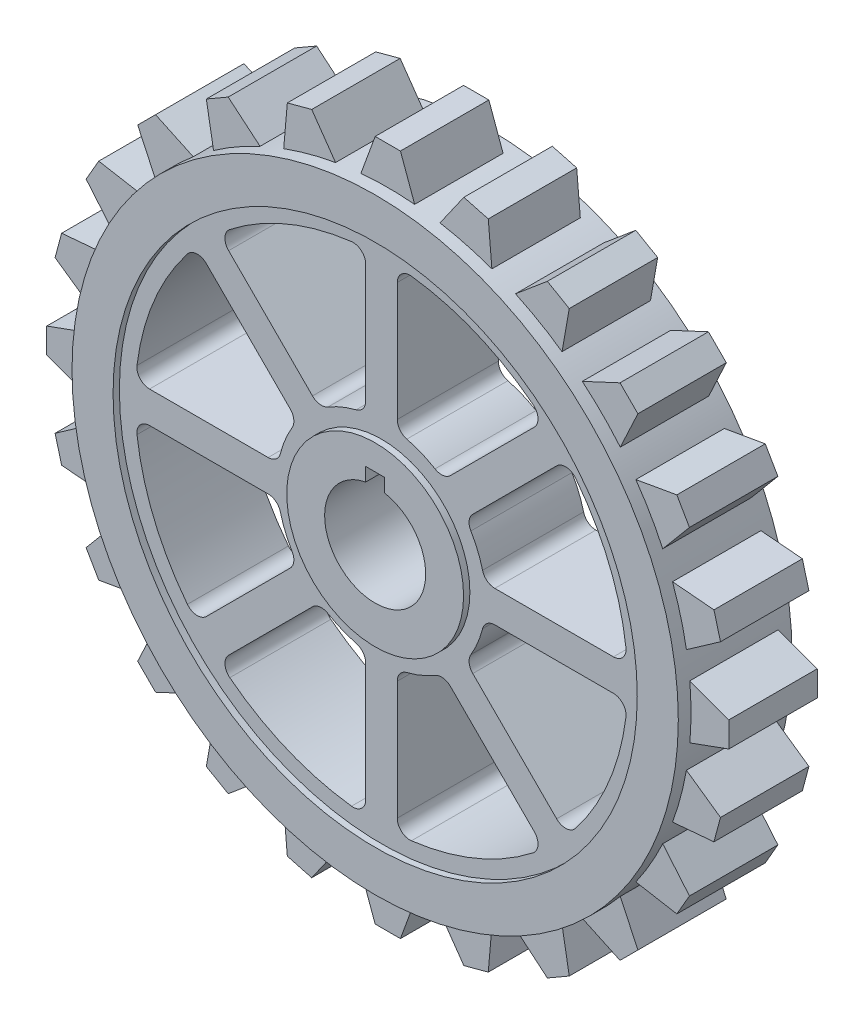
SolidWorks part; units mm, degrees
ref_plane "Front Plane" through (0, 0, 0) normal (0, 0, 1) x (1, 0, 0)
ref_plane "Top Plane" through (0, 0, 0) normal (0, 1, 0) x (1, 0, 0)
ref_plane "Right Plane" through (0, 0, 0) normal (1, 0, 0) x (0, 0, -1)
sketch "Sketch1" plane through (0, 0, 0) normal (0, 0, 1) x (1, 0, 0)
  line L0 (-1024.8275, 0) -> (-48, 0) construction
  line L1 (-1.5, 10) -> (1.5, 10)
  line L2 (-1.5, 10) -> (-1.5, 7.8581)
  line L3 (1.5, 10) -> (1.5, 7.8581)
  line L4 (0, 0) -> (0, 14)
  line L5 (-2.5, 36.7253) -> (-2.5, 17.9444)
  line L6 (0, 0) -> (0, 14)
  line L7 (24.201, 27.7365) -> (10.9208, 14.4563)
  line L8 (0, 0) -> (-25.7527, 25.7527) construction
  line L9 (-24.201, 27.7365) -> (-10.9208, 14.4563)
  line L10 (36.7253, 2.5) -> (17.9444, 2.5)
  line L11 (27.7365, 24.201) -> (14.4563, 10.9208)
  line L13 (2.5, 36.7253) -> (2.5, 17.9444)
  line L14 (-36.7253, 2.5) -> (-17.9444, 2.5)
  line L15 (0, 54) -> (0, 48) construction
  line L16 (-2, 54) -> (2, 54)
  line L17 (-2, 54) -> (-4.2525, 47.8113)
  line L18 (2, 54) -> (4.2525, 47.8113)
  line L19 (12.0444, 52.6776) -> (8.2668, 47.2828)
  line L20 (12.0444, 52.6776) -> (15.9081, 51.6424)
  line L21 (15.9081, 51.6424) -> (16.4821, 45.0815)
  line L22 (25.2679, 47.7654) -> (20.2228, 43.532)
  line L23 (25.2679, 47.7654) -> (28.7321, 45.7654)
  line L24 (28.7321, 45.7654) -> (27.5884, 39.2795)
  line L25 (36.7696, 39.598) -> (30.8007, 36.8146)
  line L26 (36.7696, 39.598) -> (39.598, 36.7696)
  line L27 (39.598, 36.7696) -> (36.8146, 30.8007)
  line L28 (45.7654, 28.7321) -> (39.2795, 27.5884)
  line L29 (45.7654, 28.7321) -> (47.7654, 25.2679)
  line L30 (47.7654, 25.2679) -> (43.532, 20.2228)
  line L31 (51.6424, 15.9081) -> (45.0815, 16.4821)
  line L32 (51.6424, 15.9081) -> (52.6776, 12.0444)
  line L33 (52.6776, 12.0444) -> (47.2828, 8.2668)
  line L34 (54, 2) -> (47.8113, 4.2525)
  line L35 (54, 2) -> (54, -2)
  line L36 (54, -2) -> (47.8113, -4.2525)
  line L37 (52.6776, -12.0444) -> (47.2828, -8.2668)
  line L38 (52.6776, -12.0444) -> (51.6424, -15.9081)
  line L39 (51.6424, -15.9081) -> (45.0815, -16.4821)
  line L40 (47.7654, -25.2679) -> (43.532, -20.2228)
  line L41 (47.7654, -25.2679) -> (45.7654, -28.7321)
  line L42 (45.7654, -28.7321) -> (39.2795, -27.5884)
  line L43 (39.598, -36.7696) -> (36.8146, -30.8007)
  line L44 (39.598, -36.7696) -> (36.7696, -39.598)
  line L45 (36.7696, -39.598) -> (30.8007, -36.8146)
  line L46 (28.7321, -45.7654) -> (27.5884, -39.2795)
  line L47 (28.7321, -45.7654) -> (25.2679, -47.7654)
  line L48 (25.2679, -47.7654) -> (20.2228, -43.532)
  line L49 (15.9081, -51.6424) -> (16.4821, -45.0815)
  line L50 (15.9081, -51.6424) -> (12.0444, -52.6776)
  line L51 (12.0444, -52.6776) -> (8.2668, -47.2828)
  line L52 (2, -54) -> (4.2525, -47.8113)
  line L53 (2, -54) -> (-2, -54)
  line L54 (-2, -54) -> (-4.2525, -47.8113)
  line L55 (-12.0444, -52.6776) -> (-8.2668, -47.2828)
  line L56 (-12.0444, -52.6776) -> (-15.9081, -51.6424)
  line L57 (-15.9081, -51.6424) -> (-16.4821, -45.0815)
  line L58 (-25.2679, -47.7654) -> (-20.2228, -43.532)
  line L59 (-25.2679, -47.7654) -> (-28.7321, -45.7654)
  line L60 (-28.7321, -45.7654) -> (-27.5884, -39.2795)
  line L61 (-36.7696, -39.598) -> (-30.8007, -36.8146)
  line L62 (-36.7696, -39.598) -> (-39.598, -36.7696)
  line L63 (-39.598, -36.7696) -> (-36.8146, -30.8007)
  line L64 (-45.7654, -28.7321) -> (-39.2795, -27.5884)
  line L65 (-45.7654, -28.7321) -> (-47.7654, -25.2679)
  line L66 (-47.7654, -25.2679) -> (-43.532, -20.2228)
  line L67 (-51.6424, -15.9081) -> (-45.0815, -16.4821)
  line L68 (-51.6424, -15.9081) -> (-52.6776, -12.0444)
  line L69 (-52.6776, -12.0444) -> (-47.2828, -8.2668)
  line L70 (-54, -2) -> (-47.8113, -4.2525)
  line L71 (-54, -2) -> (-54, 2)
  line L72 (-54, 2) -> (-47.8113, 4.2525)
  line L73 (-52.6776, 12.0444) -> (-47.2828, 8.2668)
  line L74 (-52.6776, 12.0444) -> (-51.6424, 15.9081)
  line L75 (-51.6424, 15.9081) -> (-45.0815, 16.4821)
  line L76 (-47.7654, 25.2679) -> (-43.532, 20.2228)
  line L77 (-47.7654, 25.2679) -> (-45.7654, 28.7321)
  line L78 (-45.7654, 28.7321) -> (-39.2795, 27.5884)
  line L79 (-39.598, 36.7696) -> (-36.8146, 30.8007)
  line L80 (-39.598, 36.7696) -> (-36.7696, 39.598)
  line L81 (-36.7696, 39.598) -> (-30.8007, 36.8146)
  line L82 (-28.7321, 45.7654) -> (-27.5884, 39.2795)
  line L83 (-28.7321, 45.7654) -> (-25.2679, 47.7654)
  line L84 (-25.2679, 47.7654) -> (-20.2228, 43.532)
  line L85 (-15.9081, 51.6424) -> (-16.4821, 45.0815)
  line L86 (-15.9081, 51.6424) -> (-12.0444, 52.6776)
  line L87 (-12.0444, 52.6776) -> (-8.2668, 47.2828)
  line L88 (-27.7365, 24.201) -> (-14.4563, 10.9208)
  line L89 (-24.201, 27.7365) -> (-10.9208, 14.4563)
  line L90 (36.7253, -2.5) -> (17.9444, -2.5)
  line L91 (27.7365, -24.201) -> (14.4563, -10.9208)
  line L92 (24.201, -27.7365) -> (10.9208, -14.4563)
  line L93 (2.5, -36.7253) -> (2.5, -17.9444)
  line L94 (-2.5, -36.7253) -> (-2.5, -17.9444)
  line L95 (-24.201, -27.7365) -> (-10.9208, -14.4563)
  line L96 (-27.7365, -24.201) -> (-14.4563, -10.9208)
  line L97 (-36.7253, -2.5) -> (-17.9444, -2.5)
  line L98 (-14, 0) -> (24.8275, 0) construction
  arc A0 (-1.5, 7.8581) -> (1.5, 7.8581) centre (0, 0) ccw
  circle A1 centre (0, 0) radius 14
  circle A2 centre (0, 0) radius 41.5
  circle A3 centre (0, 0) radius 48
  circle A4 centre (0, 0) radius 48
  circle A5 centre (0, 0) radius 48
  circle A6 centre (0, 0) radius 48
  circle A7 centre (0, 0) radius 48
  circle A8 centre (0, 0) radius 48
  circle A9 centre (0, 0) radius 48
  circle A10 centre (0, 0) radius 48
  circle A11 centre (0, 0) radius 48
  circle A12 centre (0, 0) radius 48
  circle A13 centre (0, 0) radius 48
  circle A14 centre (0, 0) radius 48
  circle A15 centre (0, 0) radius 48
  circle A16 centre (0, 0) radius 48
  circle A17 centre (0, 0) radius 48
  circle A18 centre (0, 0) radius 48
  circle A19 centre (0, 0) radius 48
  circle A20 centre (0, 0) radius 48
  circle A21 centre (0, 0) radius 48
  circle A22 centre (0, 0) radius 48
  circle A23 centre (0, 0) radius 48
  circle A24 centre (0, 0) radius 48
  circle A25 centre (0, 0) radius 48
  circle A26 centre (0, 0) radius 48
  arc A27 (30.7264, -24.0185) -> (38.7105, -4.7432) centre (0, 0) ccw
  arc A28 (-36.7253, 2.5) -> (-38.7105, 4.7432) centre (-36.7253, 4.5) cw
  circle A29 centre (0, 0) radius 39 construction
  arc A30 (-27.7365, 24.201) -> (-30.7264, 24.0185) centre (-29.1507, 22.7868) ccw
  arc A31 (-30.7264, 24.0185) -> (-38.7105, 4.7432) centre (0, 0) ccw
  arc A32 (-24.0185, 30.7264) -> (-4.7432, 38.7105) centre (0, 0) cw
  arc A33 (-24.201, 27.7365) -> (-24.0185, 30.7264) centre (-22.7868, 29.1507) cw
  arc A34 (-2.5, 36.7253) -> (-4.7432, 38.7105) centre (-4.5, 36.7253) ccw
  arc A35 (-14.4563, 10.9208) -> (-14.1548, 8.4789) centre (-15.8706, 9.5066) cw
  arc A36 (-14.1548, 8.4789) -> (-16.0044, 4.0135) centre (0, 0) ccw
  arc A37 (-4.0135, 16.0044) -> (-8.4789, 14.1548) centre (0, 0) ccw
  arc A38 (17.9444, 2.5) -> (16.0044, 4.0135) centre (17.9444, 4.5) cw
  arc A39 (8.4789, 14.1548) -> (4.0135, 16.0044) centre (0, 0) ccw
  arc A40 (16.0044, 4.0135) -> (14.1548, 8.4789) centre (0, 0) ccw
  arc A41 (10.9208, -14.4563) -> (8.4789, -14.1548) centre (9.5066, -15.8706) ccw
  arc A42 (2.5, -17.9444) -> (4.0135, -16.0044) centre (4.5, -17.9444) cw
  arc A43 (36.7253, 2.5) -> (38.7105, 4.7432) centre (36.7253, 4.5) ccw
  arc A44 (30.7264, 24.0185) -> (38.7105, 4.7432) centre (0, 0) cw
  arc A45 (27.7365, 24.201) -> (30.7264, 24.0185) centre (29.1507, 22.7868) cw
  arc A46 (24.201, 27.7365) -> (24.0185, 30.7264) centre (22.7868, 29.1507) ccw
  arc A47 (2.5, 36.7253) -> (4.7432, 38.7105) centre (4.5, 36.7253) cw
  arc A48 (-4.7432, 38.7105) -> (-24.0185, 30.7264) centre (0, 0) ccw
  arc A49 (24.0185, 30.7264) -> (4.7432, 38.7105) centre (0, 0) ccw
  arc A50 (17.9444, -2.5) -> (16.0044, -4.0135) centre (17.9444, -4.5) ccw
  arc A51 (36.7253, -2.5) -> (38.7105, -4.7432) centre (36.7253, -4.5) cw
  arc A52 (27.7365, -24.201) -> (30.7264, -24.0185) centre (29.1507, -22.7868) ccw
  arc A53 (14.4563, -10.9208) -> (14.1548, -8.4789) centre (15.8706, -9.5066) cw
  arc A54 (24.201, -27.7365) -> (24.0185, -30.7264) centre (22.7868, -29.1507) cw
  arc A55 (24.0185, -30.7264) -> (4.7432, -38.7105) centre (0, 0) cw
  arc A56 (2.5, -36.7253) -> (4.7432, -38.7105) centre (4.5, -36.7253) ccw
  arc A57 (14.1548, -8.4789) -> (16.0044, -4.0135) centre (0, 0) ccw
  arc A58 (4.0135, -16.0044) -> (8.4789, -14.1548) centre (0, 0) ccw
  arc A59 (-8.4789, -14.1548) -> (-4.0135, -16.0044) centre (0, 0) ccw
  arc A60 (-2.5, -36.7253) -> (-4.7432, -38.7105) centre (-4.5, -36.7253) cw
  arc A61 (-24.0185, -30.7264) -> (-4.7432, -38.7105) centre (0, 0) ccw
  arc A62 (-24.201, -27.7365) -> (-24.0185, -30.7264) centre (-22.7868, -29.1507) ccw
  arc A63 (-16.0044, -4.0135) -> (-14.1548, -8.4789) centre (0, 0) ccw
  arc A65 (-27.7365, -24.201) -> (-30.7264, -24.0185) centre (-29.1507, -22.7868) cw
  arc A66 (-30.7264, -24.0185) -> (-38.7105, -4.7432) centre (0, 0) cw
  arc A67 (-36.7253, -2.5) -> (-38.7105, -4.7432) centre (-36.7253, -4.5) ccw
  arc A68 (38.7105, 4.7432) -> (30.7264, 24.0185) centre (0, 0) ccw
  arc A72 (-17.9444, 2.5) -> (-16.0044, 4.0135) centre (-17.9444, 4.5) ccw
  arc A73 (-10.9208, 14.4563) -> (-8.4789, 14.1548) centre (-9.5066, 15.8706) ccw
  arc A74 (-2.5, 17.9444) -> (-4.0135, 16.0044) centre (-4.5, 17.9444) cw
  arc A75 (14.4563, 10.9208) -> (14.1548, 8.4789) centre (15.8706, 9.5066) ccw
  arc A76 (10.9208, 14.4563) -> (8.4789, 14.1548) centre (9.5066, 15.8706) cw
  arc A77 (2.5, 17.9444) -> (4.0135, 16.0044) centre (4.5, 17.9444) ccw
  arc A78 (-2.5, -17.9444) -> (-4.0135, -16.0044) centre (-4.5, -17.9444) ccw
  arc A79 (-10.9208, -14.4563) -> (-8.4789, -14.1548) centre (-9.5066, -15.8706) cw
  arc A80 (-14.4563, -10.9208) -> (-14.1548, -8.4789) centre (-15.8706, -9.5066) ccw
  arc A81 (-17.9444, -2.5) -> (-16.0044, -4.0135) centre (-17.9444, -4.5) cw
  point P7 (0, 10)
  point P10 (0, 0)
  point P15 (1.1145, 38.5739)
  point P24 (0, 0)
  point P34 (0, 54)
  point P154 (0, 0)
  point P156 (-24.0185, 30.7264)
  point P166 (-24.201, 27.7365)
  point P167 (0, 0)
  point P170 (0, 0)
  dimension "D1" = 8
  dimension "D4" = 28
  dimension "D10" = 6.5
  dimension "D12" = 4
  dimension "D5" = 2
  dimension "D13" = 2
  dimension "D16" = 2
  dimension "D2" = 3
  dimension "D3" = 10
  dimension "D6" = 40
  dimension "D7" = 6
  dimension "D9" = 108
  dimension "D14" = 4
  dimension "D11" = 2.5
  dimension "D8" = 24
extrude "Boss-Extrude1" add sketch "Sketch1" along normal mid plane 18 contours A3 A2 region at (0, 46.6424, 0)
extrude "Boss-Extrude2" add sketch "Sketch1<5>" along normal mid plane 14 contours A3 L87 L86 L85 | A3 L18 L16 L17 | A3 L21 L20 L19 | A3 L24 L23 L22 | A3 L27 L26 L25 | A3 L30 L29 L28 | A3 L33 L32 L31 | A3 L36 L35 L34 | A3 L39 L38 L37 | A3 L42 L41 L40 | A3 L45 L44 L43 | A3 L48 L47 L46 | A3 L51 L50 L49 | A3 L54 L53 L52 | A3 L57 L56 L55 | A3 L60 L59 L58 | A3 L63 L62 L61 | A3 L66 L65 L64 | A3 L69 L68 L67 | A3 L72 L71 L70 | A3 L75 L74 L73 | A3 L78 L77 L76 | A3 L81 L80 L79 | A3 L84 L83 L82 region at (0, 50.6094, 0) region at (-13.0987, 48.8849, 0) region at (13.0987, 48.8849, 0) region at (-25.3047, 43.829, 0) region at (25.3047, 43.829, 0) region at (-35.7862, 35.7862, 0) region at (35.7862, 35.7862, 0) region at (-43.829, 25.3047, 0) region at (43.829, 25.3047, 0) region at (-48.8849, 13.0987, 0) region at (48.8849, 13.0987, 0) region at (-50.6094, 0, 0) region at (50.6094, 0, 0) region at (-48.8849, -13.0987, 0) region at (48.8849, -13.0987, 0) region at (-43.829, -25.3047, 0) region at (43.829, -25.3047, 0) region at (-35.7862, -35.7862, 0) region at (35.7862, -35.7862, 0) region at (-25.3047, -43.829, 0) region at (25.3047, -43.829, 0) region at (-13.0987, -48.8849, 0) region at (13.0987, -48.8849, 0) region at (0, -50.6094, 0)
sketch "Sketch1<5>" plane through (0, 0, 0) normal (0, 0, 1) x (1, 0, 0) same geometry as "Sketch1"
extrude "Boss-Extrude3" add sketch "Sketch1<8>" along normal mid plane 16 contours A2 A77 L13 A47 A49 A46 L7 A76 A39 A75 L11 A45 A44 A43 L10 A38 A40 A72 L14 A28 A31 A30 L88 A35 A36 A1 A53 A57 A50 L90 A51 A27 A52 L91 A42 A58 A41 L92 A54 A55 A56 L93 L5 A74 region at (-40.3262, 0, 0)
sketch "Sketch1<8>" plane through (0, 0, 0) normal (0, 0, 1) x (1, 0, 0) same geometry as "Sketch1"
extrude "Boss-Extrude4" add sketch "Sketch1<9>" along normal mid plane 18 contours A1 L1 L3 A0 L2 region at (9.6195, 9.6195, 0)
sketch "Sketch1<9>" plane through (0, 0, 0) normal (0, 0, 1) x (1, 0, 0) same geometry as "Sketch1"
